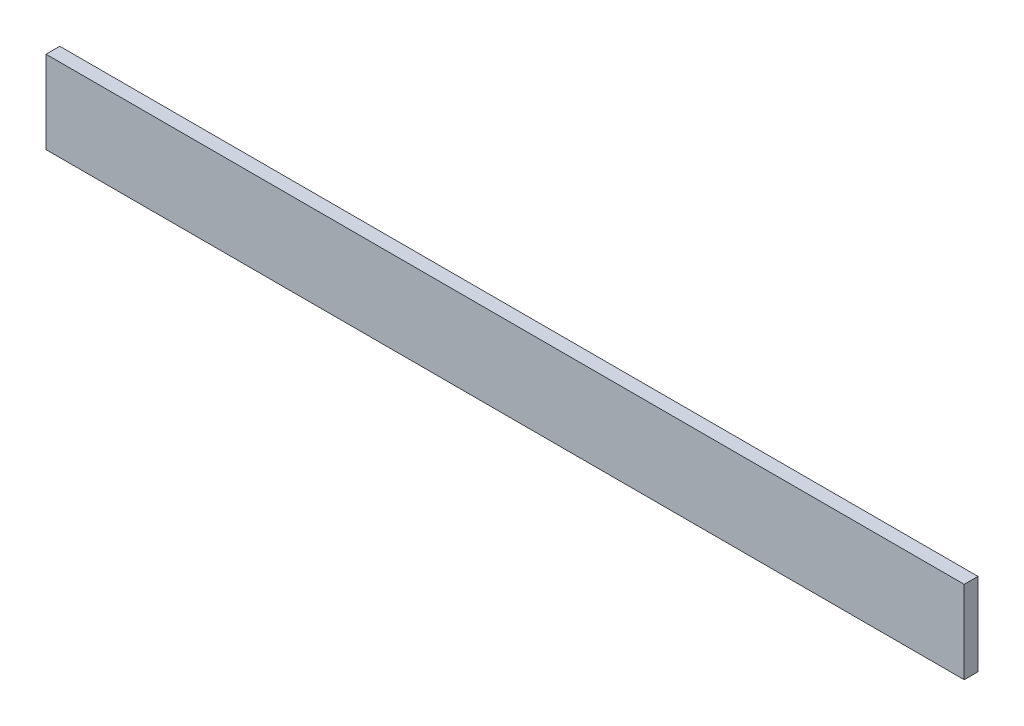
SolidWorks part; units mm, degrees
ref_plane "Front Plane" through (0, 0, 0) normal (0, 0, 1) x (1, 0, 0)
ref_plane "Top Plane" through (0, 0, 0) normal (0, 1, 0) x (1, 0, 0)
ref_plane "Right Plane" through (0, 0, 0) normal (1, 0, 0) x (0, 0, -1)
sketch "Sketch1" plane through (0, 0, 0) normal (1, 0, 0) x (0, 0, -1)
  line L1 (-0.75, -4.5) -> (0.75, -4.5)
  line L2 (-0.75, -4.5) -> (-0.75, 4.5)
  line L3 (-0.75, 4.5) -> (0.75, 4.5)
  line L4 (0.75, -4.5) -> (0.75, 4.5)
  line L5 (-0.75, -4.5) -> (0.75, 4.5) construction
  line L6 (-0.75, 4.5) -> (0.75, -4.5) construction
  point P0 (0, 0)
  dimension "D1" = 1.5
  dimension "D2" = 9
extrude "Boss-Extrude1" add sketch "Sketch1" along normal blind 100
